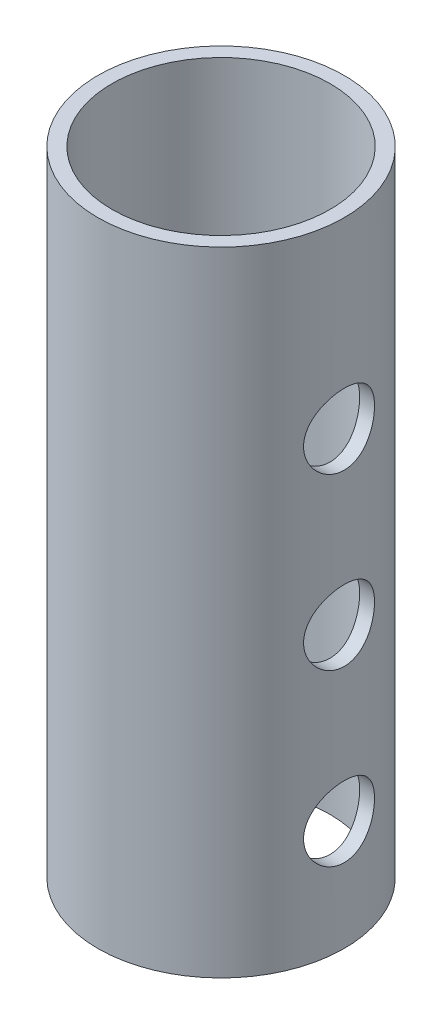
SolidWorks part; units mm, degrees
material "PTFE (general)"
ref_plane "Front Plane" through (0, 0, 0) normal (0, 0, 1) x (1, 0, 0)
ref_plane "Top Plane" through (0, 0, 0) normal (0, 1, 0) x (1, 0, 0)
ref_plane "Right Plane" through (0, 0, 0) normal (1, 0, 0) x (0, 0, -1)
sketch "Sketch1" plane through (0, 0, 0) normal (0, 1, 0) x (1, 0, 0)
  circle A0 centre (0, 0) radius 43.5
  circle A1 centre (0, 0) radius 38.5
  dimension "D1" = 87
  dimension "D2" = 77
extrude "Boss-Extrude1" add sketch "Sketch1" along normal blind 223.5
sketch "Sketch2" plane through (0, 0, 0) normal (1, 0, 0) x (0, 0, -1)
  line L0 (38.5, 223.5) -> (-38.5, 223.5) construction
  circle A0 centre (0, 158.8) radius 12.53
  circle A1 centre (0, 98.8) radius 12.53
  circle A2 centre (0, 38.8) radius 12.53
  dimension "D2" = 25.06
  dimension "D3" = 25.06
  dimension "D4" = 25.06
  dimension "D1" = 64.7
  dimension "D5" = 60
  dimension "D6" = 60
extrude "Cut-Extrude1" cut sketch "Sketch2" along normal through all
sketch "Sketch4" plane through (0, 0, 0) normal (1, 0, 0) x (0, 0, -1)
  circle A0 centre (0, 73.3) radius 7.5
  circle A4 centre (0, 98.8) radius 12.53 construction
  dimension "D1" = 15
  dimension "D3" = 25.5
extrude "Cut-Extrude2" cut sketch "Sketch4" against normal through all
